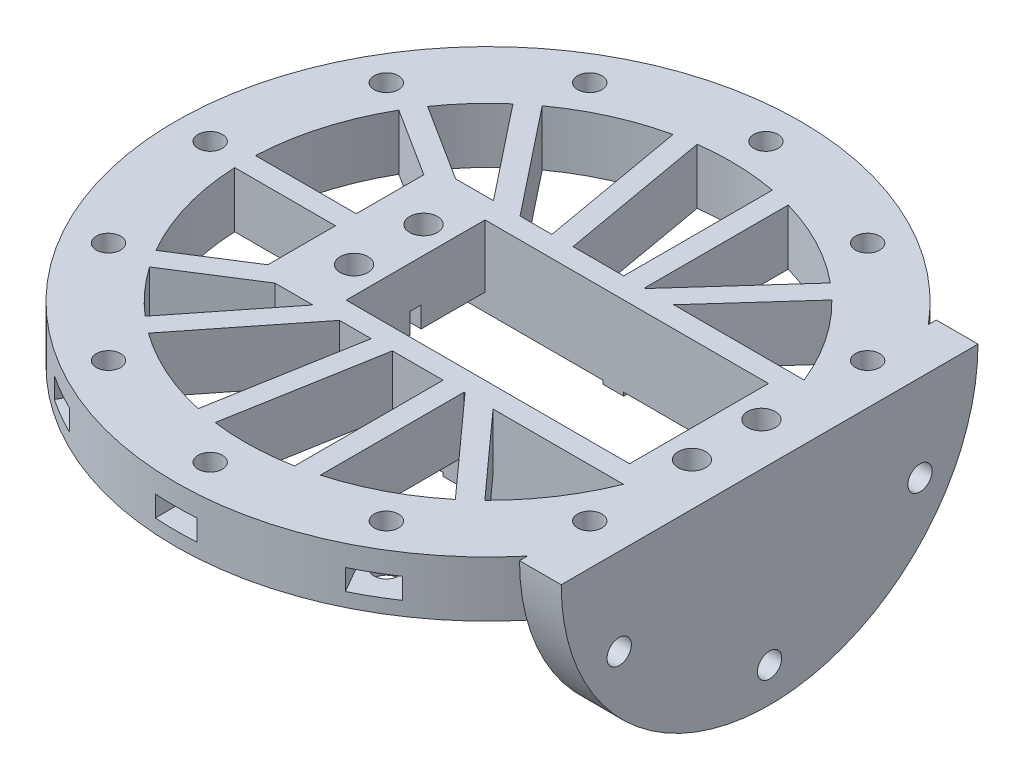
SolidWorks part; units mm, degrees
ref_plane "Front Plane" through (0, 0, 0) normal (0, 0, 1) x (1, 0, 0)
ref_plane "Top Plane" through (0, 0, 0) normal (0, 1, 0) x (1, 0, 0)
ref_plane "Right Plane" through (0, 0, 0) normal (1, 0, 0) x (0, 0, -1)
sketch "Sketch1" plane through (0, 0, 0) normal (0, 1, 0) x (1, 0, 0)
  line L0 (-43.0464, 0) -> (41.9462, 0) construction
  line L1 (0, 43.1152) -> (0, -41.8775) construction
  circle A1 centre (0, 0) radius 45
  dimension "D2" = 90
extrude "Boss-Extrude1" add sketch "Sketch1" along normal blind 12
sketch "Sketch2" plane through (0, 0, 0) normal (0, -1, 0) x (1, 0, 0)
  circle A0 centre (0, 0) radius 35
  dimension "D1" = 70
extrude "Cut-Extrude1" cut sketch "Sketch2" against normal blind 0.5
sketch "Sketch3" plane through (0, 0.5, 0) normal (0, -1, 0) x (1, 0, 0)
  line L0 (35, 0) -> (-35, 0) construction
  line L1 (0, -35) -> (0, 35) construction
  line L3 (37.5324, -10) -> (-17.4676, -10)
  line L4 (37.5324, -10) -> (37.5324, 10)
  line L5 (37.5324, 10) -> (-17.4676, 10)
  line L6 (-17.4676, -10) -> (-17.4676, 10)
  circle A0 centre (0, 0) radius 35 construction
  circle A1 centre (0, 0) radius 35 construction
  dimension "D1" = 20
  dimension "D2" = 55
  dimension "D3" = 10
  dimension "D4" = 37.5324
extrude "Cut-Extrude2" cut sketch "Sketch3" against normal blind 2.5 and the other way up to next
sketch "Sketch4" plane through (0, 3, 0) normal (0, -1, 0) x (1, 0, 0)
  line L0 (37.5324, 0) -> (-17.4676, 0) construction
  line L1 (37.5324, 10) -> (37.5324, -10) construction
  line L2 (-17.4676, 10) -> (-17.4676, -10) construction
  line L3 (0, -10) -> (0, 10) construction
  line L4 (-17.4676, -10) -> (33.541, -10) construction
  line L5 (33.541, 10) -> (-17.4676, 10) construction
  line L7 (30.3722, -10) -> (-10.4278, -10)
  line L8 (30.3722, -10) -> (30.3722, 10)
  line L9 (30.3722, 10) -> (-10.4278, 10)
  line L10 (-10.4278, -10) -> (-10.4278, 10)
  dimension "D1" = 20
  dimension "D2" = 40.8
  dimension "D3" = 30.3722
  dimension "D4" = 10
extrude "Cut-Extrude3" cut sketch "Sketch4" against normal blind 9
sketch "Sketch8" plane through (0, 0.5, 0) normal (0, -1, 0) x (1, 0, 0)
  line L0 (-17.4676, 0) -> (-35, 0) construction
  line L1 (-17.4676, 10) -> (-17.4676, -10) construction
  line L2 (8.0367, 10) -> (8.0367, 34.0648) construction
  line L3 (33.541, 10) -> (-17.4676, 10) construction
  line L4 (8.0367, -10) -> (8.0367, -29.3194) construction
  line L5 (-17.4676, -10) -> (33.541, -10) construction
  line L6 (6.5367, 10) -> (6.5367, 34.3842)
  line L7 (9.5367, 10) -> (9.5367, 33.6757)
  line L8 (9.5367, 10) -> (6.5367, 10)
  line L9 (9.5367, -10) -> (6.5367, -10)
  line L10 (6.5367, -10) -> (6.5367, -34.3842)
  line L11 (9.5367, -10) -> (9.5367, -33.6757)
  line L12 (-17.4676, 1.5) -> (-34.9678, 1.5)
  line L13 (-17.4676, -1.5) -> (-34.9678, -1.5)
  line L14 (-17.4676, 1.5) -> (-17.4676, -1.5)
  arc A0 (33.541, 10) -> (33.541, -10) centre (0, 0) ccw construction
  arc A1 (9.5367, 33.6757) -> (6.5367, 34.3842) centre (7.9531, 33.6757) ccw
  arc A2 (9.5367, -33.6757) -> (6.5367, -34.3842) centre (7.9531, -33.6757) cw
  arc A3 (-34.9678, 1.5) -> (-34.9678, -1.5) centre (-34.9678, 0) ccw
  dimension "D3" = 1.5
  dimension "D1" = 1.5
  dimension "D2" = 1.5
  dimension "D4" = 1.5
extrude "Boss-Extrude2" add sketch "Sketch8" along normal through all
sketch "Sketch16" plane through (0, 3, 0) normal (0, -1, 0) x (1, 0, 0)
  line L0 (-17.4676, 0) -> (37.5324, 0) construction
  line L1 (-17.4676, 10) -> (-17.4676, -10) construction
  line L2 (37.5324, -10) -> (37.5324, 10) construction
  line L3 (30.3722, -0.8) -> (37.5324, -0.8)
  line L4 (-10.4278, -0.8) -> (-17.4676, -0.8)
  line L5 (-10.4278, 10) -> (-10.4278, -10) construction
  line L6 (-10.4278, 0.8) -> (-17.4676, 0.8)
  line L7 (-17.4676, 0.8) -> (-17.4676, -0.8)
  line L8 (-10.4278, 0.8) -> (-10.4278, -0.8)
  line L9 (30.3722, -10) -> (30.3722, 10) construction
  line L10 (30.3722, 0.8) -> (37.5324, 0.8)
  line L11 (37.5324, 0.8) -> (37.5324, -0.8)
  line L12 (30.3722, 0.8) -> (30.3722, -0.8)
  dimension "D1" = 0.8
extrude "Cut-Extrude10" cut sketch "Sketch16" against normal blind 3
sketch "Sketch27" plane through (0, 0, 0) normal (0, -1, 0) x (1, 0, 0)
  line L0 (0, 0) -> (0, -53.17) construction
  line L1 (0, 0) -> (47.7582, -27.5732) construction
  line L3 (31.641, -18.2679) -> (31.641, -21.7321) construction
  line L4 (31.641, -21.7321) -> (34.641, -23.4641) construction
  line L5 (34.641, -23.4641) -> (37.641, -21.7321) construction
  line L6 (37.641, -21.7321) -> (37.641, -18.2679) construction
  line L7 (37.641, -18.2679) -> (34.641, -16.5359) construction
  line L8 (34.641, -16.5359) -> (31.641, -18.2679) construction
  circle A0 centre (0, 0) radius 40 construction
  circle A1 centre (34.641, -20) radius 1.75
  circle A2 centre (0, 0) radius 35 construction
  circle A3 centre (34.641, -20) radius 3 construction
  circle A4 centre (20, -34.641) radius 1.75
  circle A5 centre (0, -40) radius 1.75
  circle A6 centre (-20, -34.641) radius 1.75
  circle A7 centre (-34.641, -20) radius 1.75
  circle A8 centre (-40, 0) radius 1.75
  circle A9 centre (-34.641, 20) radius 1.75
  circle A10 centre (-20, 34.641) radius 1.75
  circle A11 centre (0, 40) radius 1.75
  circle A12 centre (20, 34.641) radius 1.75
  circle A13 centre (34.641, 20) radius 1.75
  circle A15 centre (40, 0) radius 1.75 [skipped]
  point P28 (0, 0)
  point P41 (0, 0)
  dimension "D1" = 80
  dimension "D3" = 3.5
  dimension "D4" = 70
  dimension "D5" = 6
  dimension "D6" = 12
  dimension "D2" = 60
extrude "Cut-Extrude15" cut sketch "Sketch27" against normal through all
ref_plane "Plane1" through (0, 9, 0) normal (0, 1, 0) x (1, 0, 0)
sketch "Sketch28" plane through (0, 9, 0) normal (0, 1, 0) x (1, 0, 0)
  line L0 (0, 0) -> (-54.493, 0) construction
  line L1 (-31.641, 18.2679) -> (-31.641, 21.7321)
  line L2 (-36.5359, 0) -> (-38.2679, 3)
  line L3 (-38.2679, 3) -> (-44.8999, 3)
  line L4 (-31.641, 21.7321) -> (-37.3844, 25.048)
  line L5 (-40.3844, 19.8519) -> (-34.641, 16.5359)
  line L6 (-44.8999, -3) -> (-38.2679, -3)
  line L7 (-38.2679, -3) -> (-36.5359, 0)
  line L8 (-43.4641, 0) -> (-42.5981, -1.5) [skipped]
  line L9 (-41.7321, 3) -> (-42.5981, 1.5) [skipped]
  line L10 (-34.641, 16.5359) -> (-31.641, 18.2679)
  line L11 (-18.2679, 31.641) -> (-16.5359, 34.641)
  line L12 (-16.5359, 34.641) -> (-19.8519, 40.3844)
  line L13 (-25.048, 37.3844) -> (-21.7321, 31.641)
  line L14 (-21.7321, 31.641) -> (-18.2679, 31.641)
  line L15 (0, 36.5359) -> (3, 38.2679)
  line L16 (3, 38.2679) -> (3, 44.8999)
  line L17 (-3, 44.8999) -> (-3, 38.2679)
  line L18 (-3, 38.2679) -> (0, 36.5359)
  line L19 (18.2679, 31.641) -> (21.7321, 31.641)
  line L20 (21.7321, 31.641) -> (25.048, 37.3844)
  line L21 (19.8519, 40.3844) -> (16.5359, 34.641)
  line L22 (16.5359, 34.641) -> (18.2679, 31.641)
  line L23 (31.641, 18.2679) -> (34.641, 16.5359)
  line L24 (34.641, 16.5359) -> (40.3844, 19.8519)
  line L25 (37.3844, 25.048) -> (31.641, 21.7321)
  line L26 (31.641, 21.7321) -> (31.641, 18.2679)
  line L31 (31.641, -18.2679) -> (31.641, -21.7321)
  line L32 (31.641, -21.7321) -> (37.3844, -25.048)
  line L33 (40.3844, -19.8519) -> (34.641, -16.5359)
  line L34 (34.641, -16.5359) -> (31.641, -18.2679)
  line L35 (18.2679, -31.641) -> (16.5359, -34.641)
  line L36 (16.5359, -34.641) -> (19.8519, -40.3844)
  line L37 (25.048, -37.3844) -> (21.7321, -31.641)
  line L38 (21.7321, -31.641) -> (18.2679, -31.641)
  line L39 (0, -36.5359) -> (-3, -38.2679)
  line L40 (-3, -38.2679) -> (-3, -44.8999)
  line L41 (3, -44.8999) -> (3, -38.2679)
  line L42 (3, -38.2679) -> (0, -36.5359)
  line L43 (-18.2679, -31.641) -> (-21.7321, -31.641)
  line L44 (-21.7321, -31.641) -> (-25.048, -37.3844)
  line L45 (-19.8519, -40.3844) -> (-16.5359, -34.641)
  line L46 (-16.5359, -34.641) -> (-18.2679, -31.641)
  line L47 (-31.641, -18.2679) -> (-34.641, -16.5359)
  line L48 (-34.641, -16.5359) -> (-40.3844, -19.8519)
  line L49 (-37.3844, -25.048) -> (-31.641, -21.7321)
  line L50 (-31.641, -21.7321) -> (-31.641, -18.2679)
  line L51 (36.5359, 0) -> (38.2679, -3) [skipped]
  line L52 (38.2679, -3) -> (44.8999, -3) [skipped]
  line L53 (44.8999, 3) -> (38.2679, 3) [skipped]
  line L54 (38.2679, 3) -> (36.5359, 0) [skipped]
  arc A0 (-44.8999, 3) -> (-44.8999, -3) centre (0, 0) ccw
  circle A1 centre (-40, 0) radius 3 construction
  arc A2 (-37.3844, 25.048) -> (-40.3844, 19.8519) centre (0, 0) ccw
  circle A3 centre (-34.641, 20) radius 3 construction
  arc A4 (-19.8519, 40.3844) -> (-25.048, 37.3844) centre (0, 0) ccw
  circle A5 centre (-20, 34.641) radius 3 construction
  arc A6 (3, 44.8999) -> (-3, 44.8999) centre (0, 0) ccw
  circle A7 centre (0, 40) radius 3 construction
  arc A8 (25.048, 37.3844) -> (19.8519, 40.3844) centre (0, 0) ccw
  circle A9 centre (20, 34.641) radius 3 construction
  arc A10 (40.3844, 19.8519) -> (37.3844, 25.048) centre (0, 0) ccw
  circle A11 centre (34.641, 20) radius 3 construction
  arc A14 (37.3844, -25.048) -> (40.3844, -19.8519) centre (0, 0) ccw
  circle A15 centre (34.641, -20) radius 3 construction
  arc A16 (19.8519, -40.3844) -> (25.048, -37.3844) centre (0, 0) ccw
  circle A17 centre (20, -34.641) radius 3 construction
  arc A18 (-3, -44.8999) -> (3, -44.8999) centre (0, 0) ccw
  circle A19 centre (0, -40) radius 3 construction
  arc A20 (-25.048, -37.3844) -> (-19.8519, -40.3844) centre (0, 0) ccw
  circle A21 centre (-20, -34.641) radius 3 construction
  arc A22 (-40.3844, -19.8519) -> (-37.3844, -25.048) centre (0, 0) ccw
  circle A23 centre (-34.641, -20) radius 3 construction
  arc A24 (44.8999, -3) -> (44.8999, 3) centre (0, 0) ccw [skipped]
  circle A25 centre (40, 0) radius 3 construction
  point P94 (0, 0)
  dimension "D1" = 90
  dimension "D2" = 6
  dimension "D3" = 12
extrude "Cut-Extrude17" cut sketch "Sketch28" against normal blind 3
sketch "Sketch29" plane through (0, 0.5, 0) normal (0, -1, 0) x (1, 0, 0)
  line L0 (32.4962, -13) -> (13.7255, -13)
  line L1 (9.5367, -33.6757) -> (9.5367, -10) construction
  line L2 (9.5367, -13) -> (9.5367, -33.6757)
  line L3 (9.5367, -10) -> (33.541, -10) construction
  line L4 (6.5367, -13) -> (-0.7691, -13)
  line L5 (6.5367, -10) -> (6.5367, -34.3842) construction
  line L6 (-20.4676, -11.223) -> (-20.4676, -1.5)
  line L7 (-34.9678, -1.5) -> (-17.4676, -1.5) construction
  line L8 (-20.4676, -1.5) -> (-34.9678, -1.5)
  line L9 (-17.4676, -0.8) -> (-17.4676, -10) construction
  line L10 (32.4962, 13) -> (13.7255, 13)
  line L11 (9.5367, 10) -> (9.5367, 33.6757) construction
  line L12 (9.5367, 13) -> (9.5367, 33.6757)
  line L13 (-7.5493, 34.1761) -> (-3.8154, 13)
  line L14 (6.5367, 13) -> (-0.7691, 13)
  line L15 (6.5367, 34.3842) -> (6.5367, 10) construction
  line L16 (-20.4676, 11.223) -> (-20.4676, 1.5)
  line L17 (-17.4676, 1.5) -> (-34.9678, 1.5) construction
  line L18 (-20.4676, 1.5) -> (-34.9678, 1.5)
  line L19 (6.5367, 13) -> (6.5367, 34.3842)
  line L20 (6.5367, -34.3842) -> (6.5367, -13)
  line L21 (0, 0) -> (-21.7353, -27.4331) construction
  line L22 (-20.5397, -28.3394) -> (-8.3862, -13)
  line L23 (-22.8911, -26.4764) -> (-12.2137, -13)
  line L24 (0, 0) -> (-20.4676, -13) construction
  line L25 (-17.6698, -13) -> (-28.713, -20.0141)
  line L26 (-20.4676, -11.223) -> (-30.3215, -17.4817)
  line L27 (0, 0) -> (-35, 0) construction
  line L28 (-20.4676, 11.223) -> (-30.3215, 17.4817)
  line L29 (-17.6698, 13) -> (-28.713, 20.0141)
  line L30 (-22.8911, 26.4764) -> (-12.2137, 13)
  line L31 (-20.5397, 28.3394) -> (-8.3862, 13)
  line L32 (-12.2137, 13) -> (-17.6698, 13)
  line L33 (0, 0) -> (-6.0777, -34.4683) construction
  line L34 (-4.5949, -34.6971) -> (-0.7691, -13)
  line L35 (-7.5493, -34.1761) -> (-3.8154, -13)
  line L36 (-3.8154, -13) -> (-17.6698, -13)
  line L37 (-4.5949, 34.6971) -> (-0.7691, 13)
  line L38 (-3.8154, 13) -> (-8.3862, 13)
  line L39 (0, 0) -> (23.4214, -26.0084) construction
  line L40 (9.6883, -13) -> (22.2852, -26.9883)
  line L41 (13.7255, -13) -> (24.5145, -24.9808)
  line L42 (13.7255, 13) -> (24.5145, 24.9808)
  line L43 (9.6883, 13) -> (22.2852, 26.9883)
  line L44 (9.6883, -13) -> (9.5367, -13)
  line L45 (9.6883, 13) -> (9.5367, 13)
  arc A0 (9.5367, -33.6757) -> (22.2852, -26.9883) centre (0, 0) ccw
  arc A1 (6.5367, 34.3842) -> (-4.5949, 34.6971) centre (0, 0) ccw
  arc A2 (32.4962, 13) -> (24.5145, 24.9808) centre (0, 0) ccw
  arc A3 (-34.9678, -1.5) -> (-30.3215, -17.4817) centre (0, 0) ccw
  circle A4 centre (0, 0) radius 35 construction
  arc A5 (-7.5493, 34.1761) -> (-20.5397, 28.3394) centre (0, 0) ccw
  arc A6 (-4.5949, -34.6971) -> (6.5367, -34.3842) centre (0, 0) ccw
  arc A7 (-20.5397, -28.3394) -> (-7.5493, -34.1761) centre (0, 0) ccw
  arc A8 (-28.713, -20.0141) -> (-22.8911, -26.4764) centre (0, 0) ccw
  arc A9 (-30.3215, 17.4817) -> (-34.9678, 1.5) centre (0, 0) ccw
  arc A10 (-22.8911, 26.4764) -> (-28.713, 20.0141) centre (0, 0) ccw
  arc A11 (24.5145, -24.9808) -> (32.4962, -13) centre (0, 0) ccw
  arc A12 (22.2852, 26.9883) -> (9.5367, 33.6757) centre (0, 0) ccw
  point P11 (21.5389, -10)
  point P23 (-17.4676, -5.4)
  line M3 (-17.4676, -1.5) -> (-34.9678, -1.5)
  arc M4 (-34.9678, -1.5) -> (6.5367, -34.3842) centre (0, 0) ccw
  line M5 (6.5367, -34.3842) -> (6.5367, -10)
  dimension "D1" = 1.5
  dimension "D2" = 3
  dimension "D3" = 3
  dimension "D4" = 80
  dimension "D5" = 1.5
  dimension "D6" = 1.5
  dimension "D7" = 1.5
sketch "Sketch32" plane through (0, 3, 0) normal (0, -1, 0) x (1, 0, 0)
  line L0 (-17.4676, 0) -> (37.5324, 0) construction
  line L1 (-17.4676, -1.5) -> (-17.4676, 1.5) construction
  line L2 (37.5324, 10) -> (37.5324, -10) construction
  line L3 (10.0324, 0) -> (10.0324, -10) construction
  line L6 (9.5367, -10) -> (33.541, -10) construction
  circle A0 centre (-14.2876, -5) radius 2
  circle A1 centre (-14.2876, 5) radius 2
  circle A2 centre (34.3524, -5) radius 2
  circle A3 centre (34.3524, 5) radius 2
  dimension "D1" = 24.32
  dimension "D3" = 4
  dimension "D2" = 5
extrude "Cut-Extrude21" cut sketch "Sketch32" against normal through all
extrude "Cut-Extrude22" cut sketch "Sketch29" against normal blind 12 contours L28 A9 L18 L16 | L26 L6 M3 M4 | L23 L36 L25 M4 | L35 L36 L22 M4 | L34 L4 M4 M5 | L2 A0 L40 L44 | L41 A11 L0 | L10 A2 L42 | L43 A12 L12 L45 | L19 A1 L37 L14 | L13 A5 L31 L38 | L30 A10 L29 L32 region at (23.89, 0.5, -17.1237) region at (13.9029, 0.5, -24.813) region at (1.8383, 0.5, -24.6789) region at (-27.5459, 0.5, -7.8919) region at (-10.8152, 0.5, -24.1049) region at (-20.9968, 0.5, -18.9781) region at (23.89, 0.5, 17.1237) region at (13.9029, 0.5, 24.813) region at (-10.8152, 0.5, 24.1049) region at (1.8383, 0.5, 24.6789) region at (-27.5459, 0.5, 7.8919) region at (-20.9968, 0.5, 18.9781)
sketch "Sketch33" plane through (0, 0, 0) normal (0, -1, 0) x (1, 0, 0)
  line L0 (37.5324, 0) -> (37.5324, 38.7806) construction
  line L1 (37.5324, 10) -> (37.5324, -10) construction
  line L3 (37.5324, 38.7806) -> (47.0341, 38.7806)
  line L4 (37.5324, 38.7806) -> (37.5324, -37.2389)
  line L5 (37.5324, -37.2389) -> (47.0341, -37.2389)
  line L6 (47.0341, 38.7806) -> (47.0341, -37.2389)
extrude "Cut-Extrude24" cut sketch "Sketch33" against normal through all
sketch "Sketch34" plane through (37.5324, 0, 0) normal (1, 0, 0) x (0, 0, -1)
  line L0 (-24.8258, 12) -> (24.8258, 12) construction
  line L1 (30, 12) -> (-30, 12)
  arc A0 (-30, 12) -> (30, 12) centre (0, 12) ccw
  dimension "D1" = 30
  dimension "D2" = 60
extrude "Boss-Extrude3" add sketch "Sketch34" along normal blind 3
sketch "Sketch35" plane through (37.5324, 0, 0) normal (-1, 0, 0) x (0, 0, 1)
  line L0 (24.8258, 0) -> (10, 0) construction
  line L1 (13, 0) -> (50, 0)
  line L2 (13, 0) -> (13, 4)
  line L3 (13, 4) -> (50, 4)
  line L4 (50, 0) -> (50, 4)
  line L5 (40.3844, 6) -> (37.3844, 6) construction
  line L6 (0, 6) -> (0, 9) construction
  line L7 (-13, 0) -> (-13, 4)
  line L8 (-13, 4) -> (-50, 4)
  line L9 (-13, 0) -> (-50, 0)
  line L10 (-50, 0) -> (-50, 4)
  dimension "D1" = 2
  dimension "D2" = 13
  dimension "D3" = 50
extrude "Cut-Extrude26" cut sketch "Sketch35" along normal blind 90
sketch "Sketch36" plane through (0, 0, 0) normal (0, 0, 1) x (1, 0, 0)
  line L0 (-17.4676, 0) -> (-17.4676, 0.5)
  line L1 (-17.4676, 0.5) -> (-20.4676, 0.5)
  line L2 (-20.4676, 0.5) -> (-23.2653, 4)
  line L3 (-23.2653, 4) -> (-47.4962, 4)
  line L4 (-47.4962, 4) -> (-47.4962, 0)
  line L5 (-47.4962, 0) -> (-17.4676, 0)
  line L6 (-32.4962, 0) -> (-32.4962, 4) construction
  dimension "D1" = 15
extrude "Cut-Extrude27" cut sketch "Sketch36" against normal through all both and the other way through all
sketch "Sketch37" plane through (40.5324, 0, 0) normal (1, 0, 0) x (0, 0, -1)
  line L0 (0, 12) -> (0, -18) construction
  line L1 (30, 12) -> (-30, 12) construction
  arc A0 (-30, 12) -> (30, 12) centre (0, 12) ccw construction
  circle A1 centre (0, -13) radius 1.75
  circle A2 centre (-21.6506, -0.5) radius 1.75
  circle A6 centre (21.6506, -0.5) radius 1.75
  circle A7 centre (-21.6506, 24.5) radius 1.75 [skipped]
  circle A8 centre (0, 37) radius 1.75 [skipped]
  circle A9 centre (21.6506, 24.5) radius 1.75 [skipped]
  point P21 (0, 12)
  dimension "D2" = 3.5
  dimension "D1" = 25
  dimension "D3" = 6
extrude "Cut-Extrude28" cut sketch "Sketch37" against normal up to next
sketch "Sketch44" plane through (37.5324, 0, 0) normal (-1, 0, 0) x (0, 0, 1)
  line L0 (-24.8258, 12) -> (-24.8258, 4)
  line L1 (-24.8258, 4) -> (-13, 4)
  line L2 (-13, 4) -> (-13, 0)
  line L3 (-13, 0) -> (-10, 0)
  line L4 (-10, 0) -> (-10, -16.2843)
  line L5 (-24.8258, 12) -> (-30, 12)
  line L6 (45, 12) -> (-45, 12) construction
  line L7 (0, 12) -> (0, -24.0756) construction
  line L8 (10, 0) -> (10, -16.2843)
  line L9 (13, 0) -> (10, 0)
  line L10 (13, 4) -> (13, 0)
  line L11 (24.8258, 4) -> (13, 4)
  line L12 (24.8258, 12) -> (30, 12)
  line L13 (24.8258, 12) -> (24.8258, 4)
  arc A0 (-30, 12) -> (30, 12) centre (0, 12) ccw construction
  arc A1 (-30, 12) -> (-10, -16.2843) centre (0, 12) ccw
  arc A2 (30, 12) -> (10, -16.2843) centre (0, 12) cw
  circle M8 centre (21.6506, -0.5) radius 1.75
  circle M9 centre (-21.6506, -0.5) radius 1.75
  line M11 (-13, 4) -> (-24.8258, 4)
  line M12 (-24.8258, 4) -> (-24.8258, 6)
  line M16 (-24.8258, 9) -> (-24.8258, 12)
  line M17 (-24.8258, 12) -> (-30, 12)
  arc M18 (-30, 12) -> (30, 12) centre (0, 12) ccw
  line M19 (30, 12) -> (24.8258, 12)
  line M20 (24.8258, 12) -> (24.8258, 9)
  line M24 (24.8258, 6) -> (24.8258, 4)
  line M25 (24.8258, 4) -> (13, 4)
  line M26 (13, 4) -> (13, 0)
  line M27 (13, 0) -> (10, 0)
  line M35 (-10, 0) -> (-13, 0)
  line M36 (-13, 0) -> (-13, 4)
extrude "Boss-Extrude7" add sketch "Sketch44" along normal blind 3 contours L13 L8 M20 M24 M25 M26 M27 M18 M19 M8 | L4 L0 M35 M36 M11 M12 M16 M17 M18 M9 region at (37.5324, -2.5142, 18.844) region at (37.5324, -2.5142, -18.844)
sketch "Sketch45" plane through (34.5324, 0, 0) normal (-1, 0, 0) x (0, 0, 1)
  line L0 (0, 0) -> (0, -20.9828) construction
  circle A0 centre (-21.6506, -0.5) radius 3.25
  circle A1 centre (21.6506, -0.5) radius 3.25
  dimension "D1" = 6.5
extrude "Cut-Extrude30" cut sketch "Sketch45" against normal blind 3
